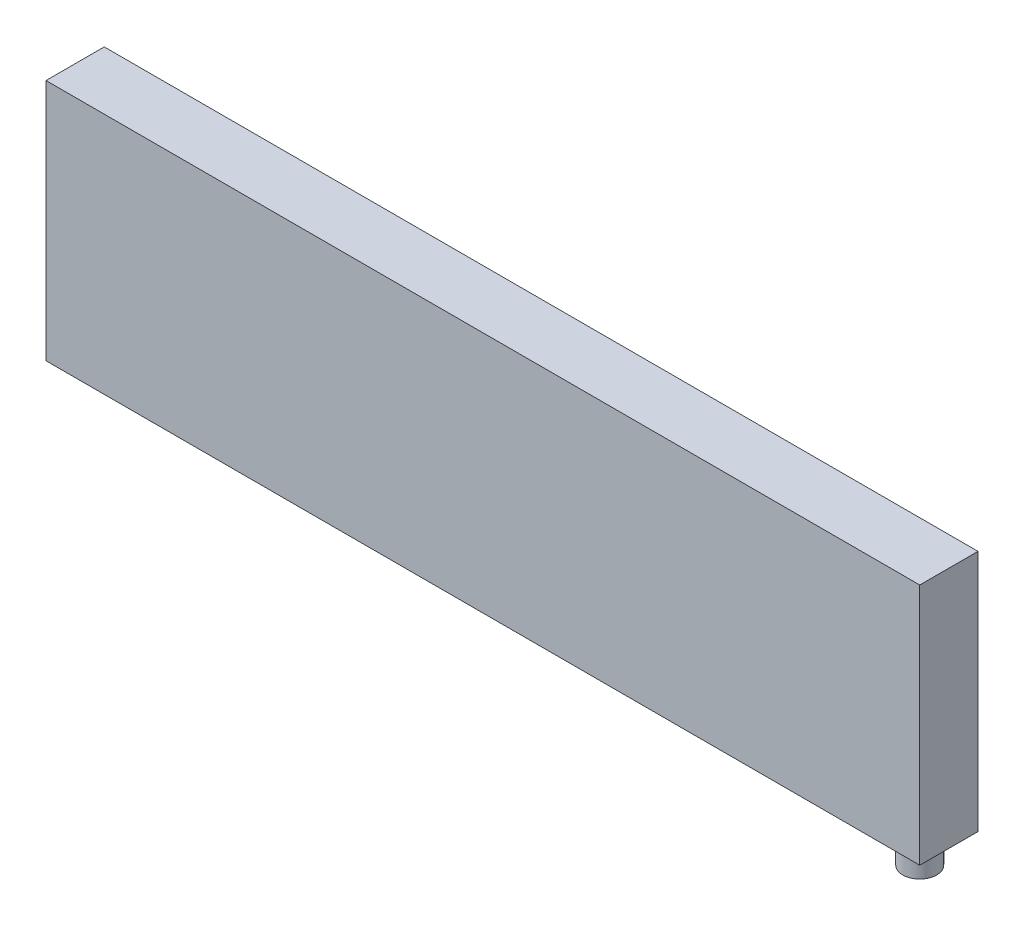
SolidWorks part; units mm, degrees
material "Teak"
ref_plane "Front Plane" through (0, 0, 0) normal (0, 0, 1) x (1, 0, 0)
ref_plane "Top Plane" through (0, 0, 0) normal (0, 1, 0) x (1, 0, 0)
ref_plane "Right Plane" through (0, 0, 0) normal (1, 0, 0) x (0, 0, -1)
sketch "Sketch1" plane through (0, 0, 0) normal (0, 0, 1) x (1, 0, 0)
  line L1 (-90, -25) -> (90, -25)
  line L2 (-90, -25) -> (-90, 25)
  line L3 (-90, 25) -> (90, 25)
  line L4 (90, -25) -> (90, 25)
  line L5 (-90, -25) -> (90, 25) construction
  line L6 (-90, 25) -> (90, -25) construction
  point P0 (0, 0)
  dimension "D1" = 180
  dimension "D2" = 50
extrude "Boss-Extrude2" add sketch "Sketch1" along normal blind 6 and the other way blind 6
sketch "Sketch3" plane through (0, -25, 0) normal (0, -1, 0) x (1, 0, 0)
  line L0 (90, -6) -> (90, 0) construction
  line L1 (90, -6) -> (90, 6) construction
  line L2 (90, 0) -> (84, 0) construction
  circle A0 centre (84, 0) radius 3.5
  dimension "D2" = 7
  dimension "D1" = 6
extrude "Boss-Extrude3" add sketch "Sketch3" along normal blind 6
